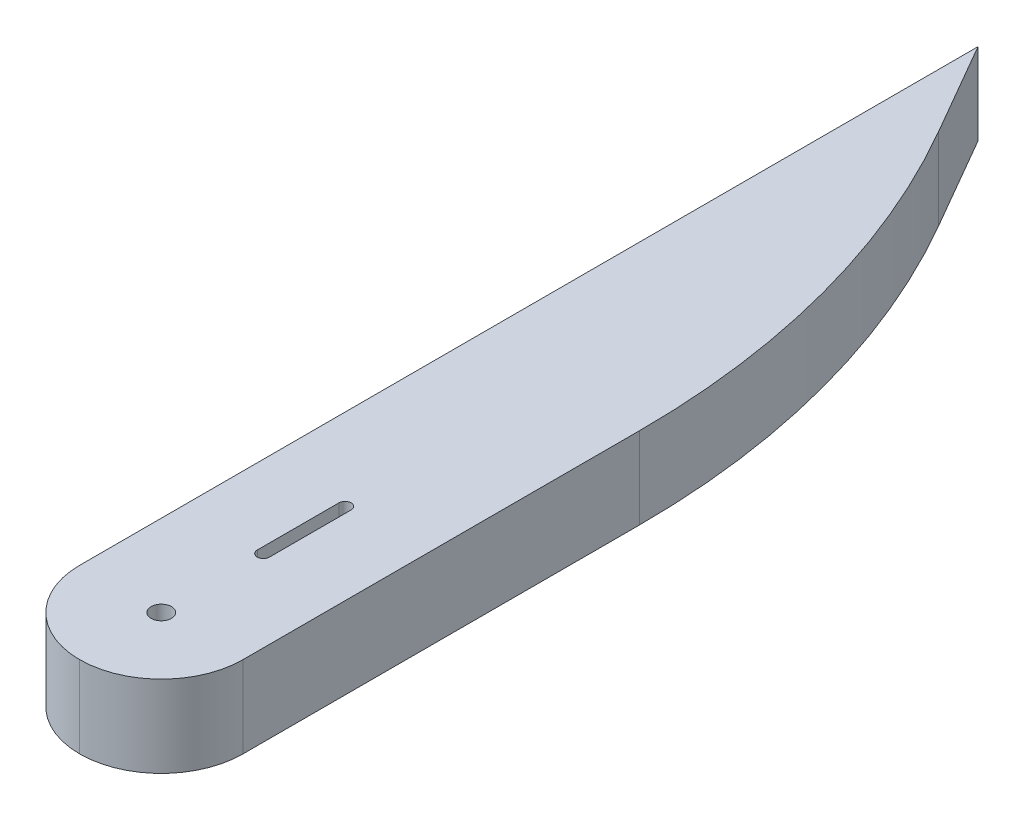
SolidWorks part; units mm, degrees
material "Oak"
ref_plane "Front" through (0, 0, 0) normal (0, 0, 1) x (1, 0, 0)
ref_plane "Top" through (0, 0, 0) normal (0, 1, 0) x (1, 0, 0)
ref_plane "Right" through (0, 0, 0) normal (1, 0, 0) x (0, 0, -1)
sketch "Sketch1" plane through (0, 0, 0) normal (0, 0, 1) x (1, 0, 0)
  line L1 (0, 0) -> (-50.8, 0)
  line L2 (0, 0) -> (0, 25.4)
  line L3 (0, 25.4) -> (-50.8, 25.4)
  line L4 (-50.8, 0) -> (-50.8, 25.4)
  dimension "D1" = 50.8
  dimension "D2" = 25.4
extrude "Boss-Extrude1" add sketch "Sketch1" along normal blind 304.8
fillet "Fillet1" radius 25.4 2 edges at (0, 12.7, 304.8) (-50.8, 12.7, 304.8)
sketch "Sketch4" plane through (-50.8, 0, 0) normal (-1, 0, 0) x (0, 0, 1)
  line L0 (0, 25.4) -> (0, 0) construction
  line L1 (304.8, 25.4) -> (279.4, 25.4) construction
  point P0 (0, 12.7)
sketch "Sketch6" plane through (0, 25.4, 0) normal (0, 1, 0) x (1, 0, 0)
  line L0 (-50.8, 0) -> (0, -87.9882)
  line L1 (0, -279.4) -> (0, 0) construction
  line L2 (0, 0) -> (-50.8, 0) construction
  line L3 (0, -87.9882) -> (0, 0)
  line L4 (0, 0) -> (-50.8, 0)
  dimension "D1" = 60
extrude "Cut-Extrude1" cut sketch "Sketch6" against normal through all
fillet "Fillet2" radius 254 1 edges at (0, 12.7, 87.9882)
sketch "Sketch7" plane through (0, 25.4, 0) normal (0, 1, 0) x (1, 0, 0)
  circle A0 centre (-25.4, -279.4) radius 3.175
  arc A1 (-25.4, -304.8) -> (0, -279.4) centre (-25.4, -279.4) ccw construction
  dimension "D1" = 6.35
extrude "Cut-Extrude2" cut sketch "Sketch7" against normal through all
sketch "Sketch8" plane through (0, 25.4, 0) normal (0, 1, 0) x (1, 0, 0)
  line L0 (-27.305, -247.65) -> (-27.305, -222.25)
  line L1 (-23.495, -247.65) -> (-23.495, -222.25)
  line L2 (-50.8, -247.65) -> (0, -247.65) construction
  line L3 (-50.8, -279.4) -> (-50.8, 0) construction
  line L4 (0, -279.4) -> (0, -156.0473) construction
  arc A0 (-23.495, -222.25) -> (-27.305, -222.25) centre (-25.4, -222.25) ccw
  arc A1 (-27.305, -247.65) -> (-23.495, -247.65) centre (-25.4, -247.65) ccw
  dimension "D1" = 25.4
  dimension "D2" = 3.81
  dimension "D3" = 57.15
extrude "Cut-Extrude3" cut sketch "Sketch8" against normal through all
